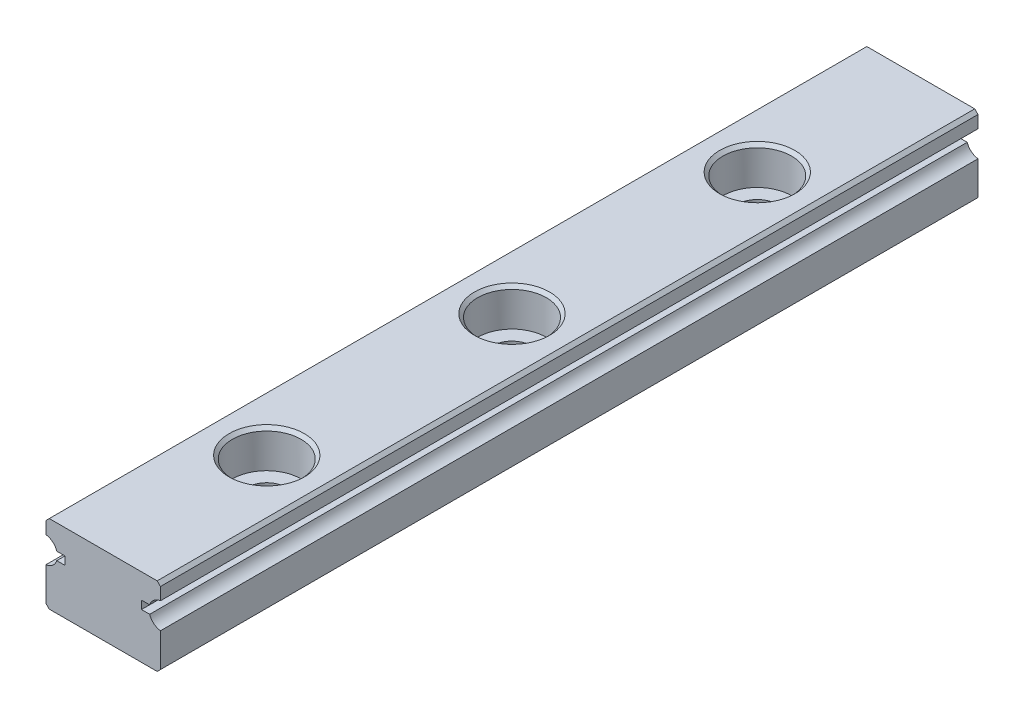
SolidWorks part; units mm, degrees
ref_plane "Спереди" through (0, 0, 0) normal (0, 0, 1) x (1, 0, 0)
ref_plane "Сверху" through (0, 0, 0) normal (0, 1, 0) x (1, 0, 0)
ref_plane "Справа" through (0, 0, 0) normal (1, 0, 0) x (0, 0, -1)
sketch "Sketch1" plane through (0, 0, 0) normal (0, 0, 1) x (1, 0, 0)
  line L0 (0, 0) -> (0, 4.3706) construction
  line L1 (-3.3, -2.4) -> (3.3, -2.4)
  line L2 (-3.5, -2.2) -> (-3.5, -0.1437)
  line L3 (-3.3, 2.4) -> (3.3, 2.4)
  line L4 (3.5, -2.2) -> (3.5, -0.1437)
  line L5 (-3.5, -2.4) -> (3.5, 2.4) construction
  line L6 (-3.5, 2.4) -> (3.5, -2.4) construction
  line L7 (-3.5, 1.4437) -> (-3.5, 2.2)
  line L8 (3.5, 1.4437) -> (3.5, 2.2)
  line L9 (-3.5, -2.2) -> (-3.3, -2.4)
  line L10 (3.3, -2.4) -> (3.5, -2.2)
  line L11 (3.3, 2.4) -> (3.5, 2.2)
  line L12 (-3.5, 2.2) -> (-3.3, 2.4)
  line L13 (2.8401, 0.4) -> (2.3401, 0.4)
  line L14 (-2.8401, 0.4) -> (-2.3401, 0.4)
  line L15 (2.3401, 0.4) -> (2.3401, 0.9)
  line L16 (-2.8401, 0.9) -> (-2.3401, 0.9)
  line L17 (-2.3401, 0.4) -> (-2.3401, 0.9)
  line L18 (2.8401, 0.9) -> (2.3401, 0.9)
  arc A0 (-3.5, 1.4437) -> (-2.8401, 0.9) centre (-3.6, 0.65) cw
  arc A1 (3.5, 1.4437) -> (2.8401, 0.9) centre (3.6, 0.65) ccw
  arc A2 (-2.8401, 0.4) -> (-3.5, -0.1437) centre (-3.6, 0.65) cw
  arc A3 (2.8401, 0.4) -> (3.5, -0.1437) centre (3.6, 0.65) ccw
  point P0 (0, 0)
  dimension "D4" = 0.8
  dimension "D5" = 0.1
  dimension "D1" = 7
  dimension "D2" = 4.8
  dimension "D3" = 1.75
  dimension "D6" = 0.5
  dimension "D7" = 0.5
  dimension "D12" = 2
extrude "Extrude1" add sketch "Sketch1" along normal blind 50
sketch "Sketch2" plane through (0, 2.4, 0) normal (0, 1, 0) x (1, 0, 0)
  line L0 (0, 0) -> (0, -10) construction
  circle A0 centre (0, -10) radius 1.2
  circle A1 centre (0, -10) radius 2.1
  dimension "D1" = 2.4
  dimension "D2" = 4.2
  dimension "D3" = 10
extrude "Extrude2" cut sketch "Sketch2" against normal up to next contours A0 region at (0, 2.4, 10)
extrude "Extrude4" cut sketch "Sketch" against normal blind 2.3
sketch "Sketch" plane through (0, 2.4, 0) normal (0, 1, 0) x (1, 0, 0) same geometry as "Sketch2"
chamfer "Chamfer1" distance 0.2 angle 45 2 edges at (0, -2.4, 11.2) (0, 2.4, 12.1)
pattern_linear "LPattern1" count 3 spacing 15 along (0, 0, 1) of "Extrude4", "Chamfer1", "Extrude2"
